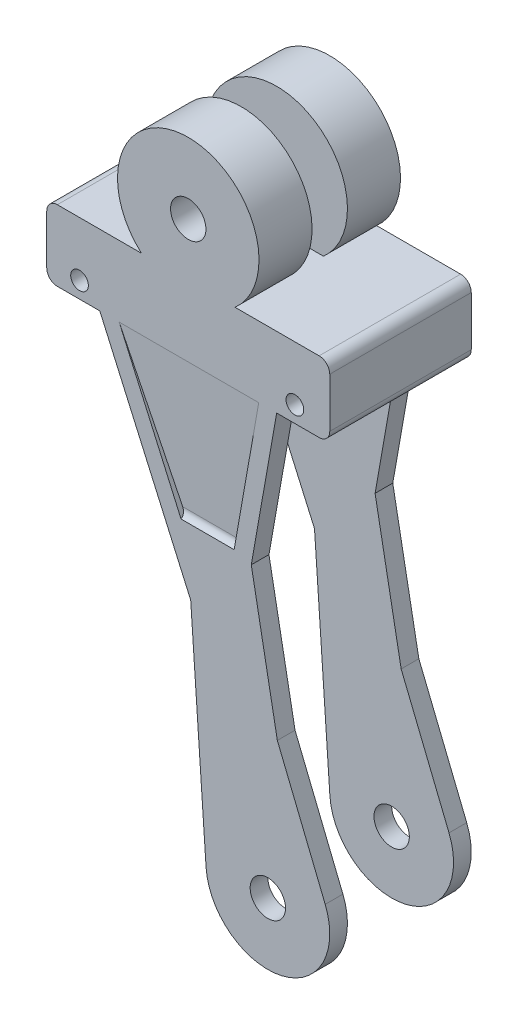
SolidWorks part; units mm, degrees
note: The reader was unsure of these and kept them because the rebuilt part matched: shared geometry of "Croquis2<4>", "Croquis4<4>", "Croquis7<2>".
material "Titanio Ti-8Al-1Mo-1V"
ref_plane "Alzado" through (0, 0, 0) normal (0, 0, 1) x (1, 0, 0)
ref_plane "Planta" through (0, 0, 0) normal (0, 1, 0) x (1, 0, 0)
ref_plane "Vista lateral" through (0, 0, 0) normal (1, 0, 0) x (0, 0, -1)
other "Centro de masa"
sketch "Croquis1" plane through (0, 0, 0) normal (0, 0, 1) x (1, 0, 0)
  line L1 (-37, 0) -> (37, 0)
  line L2 (-40, -3) -> (-40, -17)
  line L3 (-37, -20) -> (37, -20)
  line L4 (40, -3) -> (40, -17)
  arc A0 (37, 0) -> (40, -3) centre (37, -3) cw
  arc A1 (37, -20) -> (40, -17) centre (37, -17) ccw
  arc A2 (-40, -17) -> (-37, -20) centre (-37, -17) ccw
  arc A3 (-37, 0) -> (-40, -3) centre (-37, -3) ccw
  point P6 (40, 0)
  point P9 (40, -20)
  point P14 (-40, 0)
  dimension "D3" = 3
  dimension "D1" = 80
  dimension "D2" = 20
extrude "Saliente-Extruir1" add sketch "Croquis1" along normal blind 40
sketch "Croquis2" plane through (0, 0, 40) normal (0, 0, 1) x (1, 0, 0)
  line L0 (0, -20) -> (22.5, -140) construction
  line L1 (-37, -20) -> (37, -20) construction
  line L2 (40, -17) -> (40, -3) construction
  line L3 (-25, -20) -> (0.6923, -77.9551)
  line L4 (0.6923, -77.9551) -> (5.0412, -141.2005)
  line L5 (-25, -20) -> (0, -20)
  line L6 (0, -20) -> (25, -20)
  line L7 (25.1863, -100.0643) -> (17.8148, -60.7494)
  line L8 (25.1863, -100.0643) -> (38.7168, -133.4223)
  line L9 (0.6923, -77.9551) -> (10.521, -76.1122) construction
  line L10 (17.8148, -60.7494) -> (25, -20)
  arc A0 (5.0412, -141.2005) -> (38.7168, -133.4223) centre (22.5, -140) ccw
  circle A1 centre (22.5, -140) radius 5
  dimension "D2" = 35
  dimension "D8" = 10
  dimension "D1" = 120
  dimension "D3" = 25
  dimension "D4" = 10
  dimension "D5" = 40
  dimension "D6" = 10
  dimension "D7" = 80
extrude "Saliente-Extruir2" add sketch "Croquis2" against normal blind 5
extrude "Saliente-Extruir3" add sketch "Croquis2<4>" along normal blind 5 from surface at -40 starting at face at (0, -10, 0)
sketch "Croquis2<4>" plane through (0, 0, 40) normal (0, 0, 1) x (1, 0, 0) same geometry as "Croquis2"
ref_plane "Plano2" through (0, -1.4195, 40.6488) normal (0, -0.0349, 0.9994) x (1, 0, 0)
sketch "Croquis3" plane through (0, -1.4195, 40.6488) normal (0, -0.0349, 0.9994) x (1, 0, 0)
  line L0 (-19.5302, -18.5918) -> (19.9228, -18.5918)
  line L1 (19.9228, -18.5918) -> (12.9644, -58.0309)
  line L2 (12.9644, -58.0309) -> (-2.0356, -58.0309)
  line L3 (-2.0356, -58.0309) -> (-19.5302, -18.5918)
  line L4 (-25, -18.5918) -> (0.6923, -76.5117) construction
  line L5 (17.8148, -59.3164) -> (25, -18.5918) construction
  line L6 (25, -18.5918) -> (37, -18.5918) construction
  dimension "D1" = 5
  dimension "D2" = 5
  dimension "D3" = 15
extrude "Cortar-Extruir1" cut sketch "Croquis3" along normal through all
fillet "Redondeo5" radius 2 1 edges at (5.4644, -59.415, 38.6236)
ref_plane "Plano3" through (0, 0, 20) normal (0, 0, 1) x (1, 0, 0)
sketch "Croquis4" plane through (0, 0, 20) normal (0, 0, 1) x (1, 0, 0)
  line L0 (-36.4648, -15.405) -> (-36.4648, -20)
  line L1 (-37, -20) -> (-25, -20) construction
  line L2 (-25, -15.405) -> (-25, -20)
  line L3 (36.3387, -15.405) -> (36.3387, -20)
  line L4 (25, -20) -> (37, -20) construction
  line L5 (23.9618, -15.405) -> (23.9618, -20)
  line L6 (23.9618, -20) -> (36.3387, -20)
  line L7 (-36.4648, -20) -> (-25, -20)
  circle A0 centre (-30.7324, -15.405) radius 2.5
  circle A1 centre (30.1503, -15.405) radius 2.5
  arc A2 (36.3387, -15.405) -> (23.9618, -15.405) centre (30.1503, -15.405) ccw
  arc A3 (-25, -15.405) -> (-36.4648, -15.405) centre (-30.7324, -15.405) ccw
  dimension "D1" = 5
extrude "Cortar-Extruir2" cut sketch "Croquis4" against normal mid plane 10 contours L7 L2 A3 L0 | A2 L5 L6 L3
extrude "Cortar-Extruir3" cut sketch "Croquis4<4>" against normal through all both and the other way through all contours A0 | A1
sketch "Croquis4<4>" plane through (0, 0, 20) normal (0, 0, 1) x (1, 0, 0) same geometry as "Croquis4"
sketch "Croquis6" plane through (0, 0, 0) normal (0, 1, 0) x (1, 0, 0)
  line L0 (0, 0) -> (0, -40) construction
  line L1 (37, -40) -> (-37, -40) construction
  circle A0 centre (0, -20) radius 15
  dimension "D1" = 30
sketch "Croquis7" plane through (0, 0, 20) normal (0, 0, 1) x (1, 0, 0)
  line L0 (19.9228, -20) -> (-19.5302, -20) construction
  line L1 (0, 0) -> (0, 15) construction
  circle A0 centre (0, 15) radius 20
  circle A1 centre (0, 15) radius 5
  dimension "D1" = 35
  dimension "D2" = 40
  dimension "D3" = 10
extrude "Saliente-Extruir5" add sketch "Croquis7" against normal blind 15 from surface at 20 starting at face at (-28.2324, -15.405, 40)
extrude "Saliente-Extruir6" add sketch "Croquis7<2>" along normal blind 15 from surface at -20 starting at face at (-28.2324, -15.405, 0)
sketch "Croquis7<2>" plane through (0, 0, 20) normal (0, 0, 1) x (1, 0, 0) same geometry as "Croquis7"
